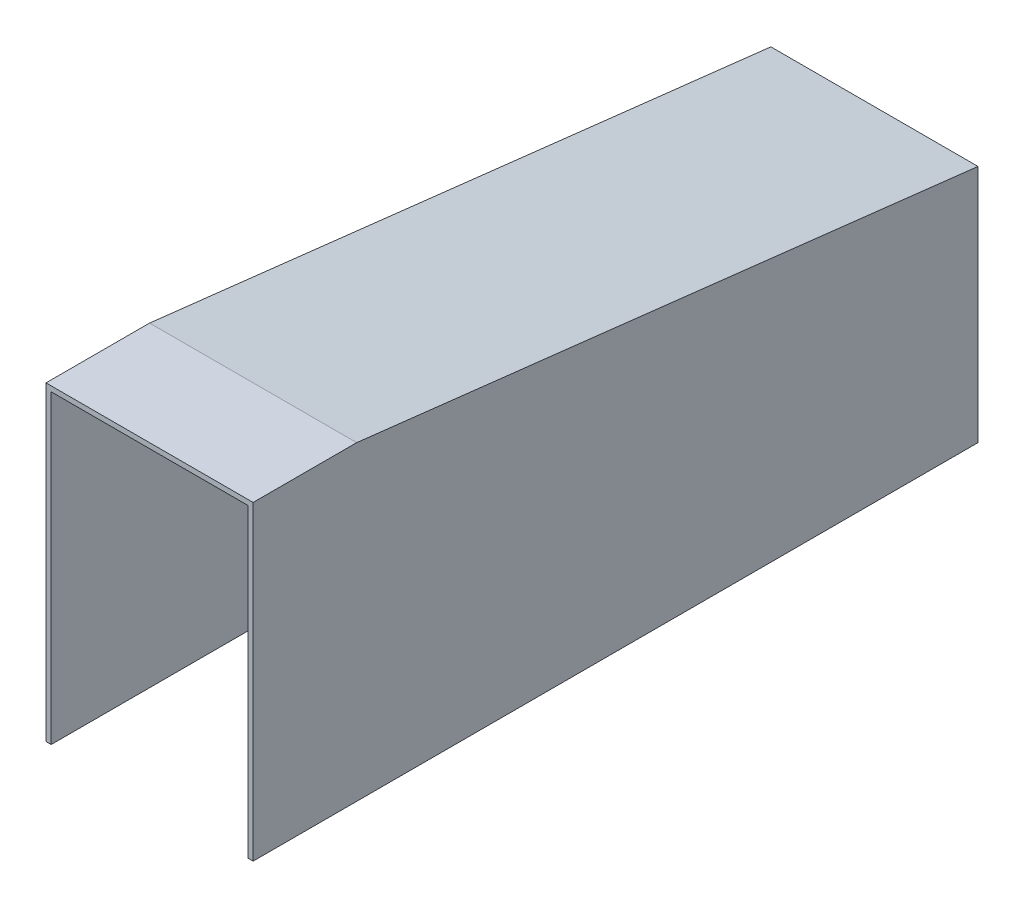
SolidWorks part; units mm, degrees
ref_plane "Front Plane" through (0, 0, 0) normal (0, 0, 1) x (1, 0, 0)
ref_plane "Top Plane" through (0, 0, 0) normal (0, 1, 0) x (1, 0, 0)
ref_plane "Right Plane" through (0, 0, 0) normal (1, 0, 0) x (0, 0, -1)
sketch "Sketch2" plane through (0, 0, 0) normal (0, 0, 1) x (1, 0, 0)
  line L1 (-25.4, -38.1) -> (25.4, -38.1)
  line L2 (-25.4, -38.1) -> (-25.4, 38.1)
  line L3 (-25.4, 38.1) -> (25.4, 38.1)
  line L4 (25.4, -38.1) -> (25.4, 38.1)
  line L5 (-25.4, -38.1) -> (25.4, 38.1) construction
  line L6 (-25.4, 38.1) -> (25.4, -38.1) construction
  point P0 (0, 0)
  dimension "D1" = 76.2
  dimension "D2" = 50.8
sketch "Sketch3" plane through (0, 0, 0) normal (1, 0, 0) x (0, 0, -1)
  line L0 (0, 38.1) -> (25.4, 38.1)
  line L1 (0, 38.1) -> (0, -38.1) construction
  line L2 (0, -38.1) -> (0, 38.1) construction
  line L3 (25.4, 38.1) -> (177.8, 20.574)
  line L4 (0, -38.1) -> (177.8, -38.1)
  line L5 (0, -38.1) -> (0, 38.1) construction
  line L6 (0, -38.1) -> (0, 38.1) construction
  line L7 (177.8, -38.1) -> (177.8, 20.574)
  line L8 (0, 38.1) -> (0, -38.1)
  dimension "D1" = 25.4
  dimension "D2" = 17.526
  dimension "D3" = 152.4
extrude "Boss-Extrude1" add sketch "Sketch3" along normal up to vertex (25.4 mm away) and the other way up to vertex (25.4 mm away) up to point (25.4, 38.1, 0) other way up to point (-25.4, 38.1, 0)
shell "Shell1" thickness 1.27 removed face at (0, 0, 0) removed face at (0, -38.1, -88.9)
sketch "Sketch4" plane through (0, 0, -177.8) normal (0, 0, -1) x (-1, 0, 0)
  line L0 (-25.4, 20.574) -> (25.4, 20.574) construction
  line L1 (25.4, 38.1) -> (-25.4, 38.1) construction
  circle A0 centre (0, -10.3075) radius 5.5626
  point P4 (0, 0)
  point P5 (0, 20.574)
  dimension "D1" = 48.4075
  dimension "D2" = 11.1252
extrude "Cut-Extrude1" cut sketch "Sketch4" against normal blind 2.54
